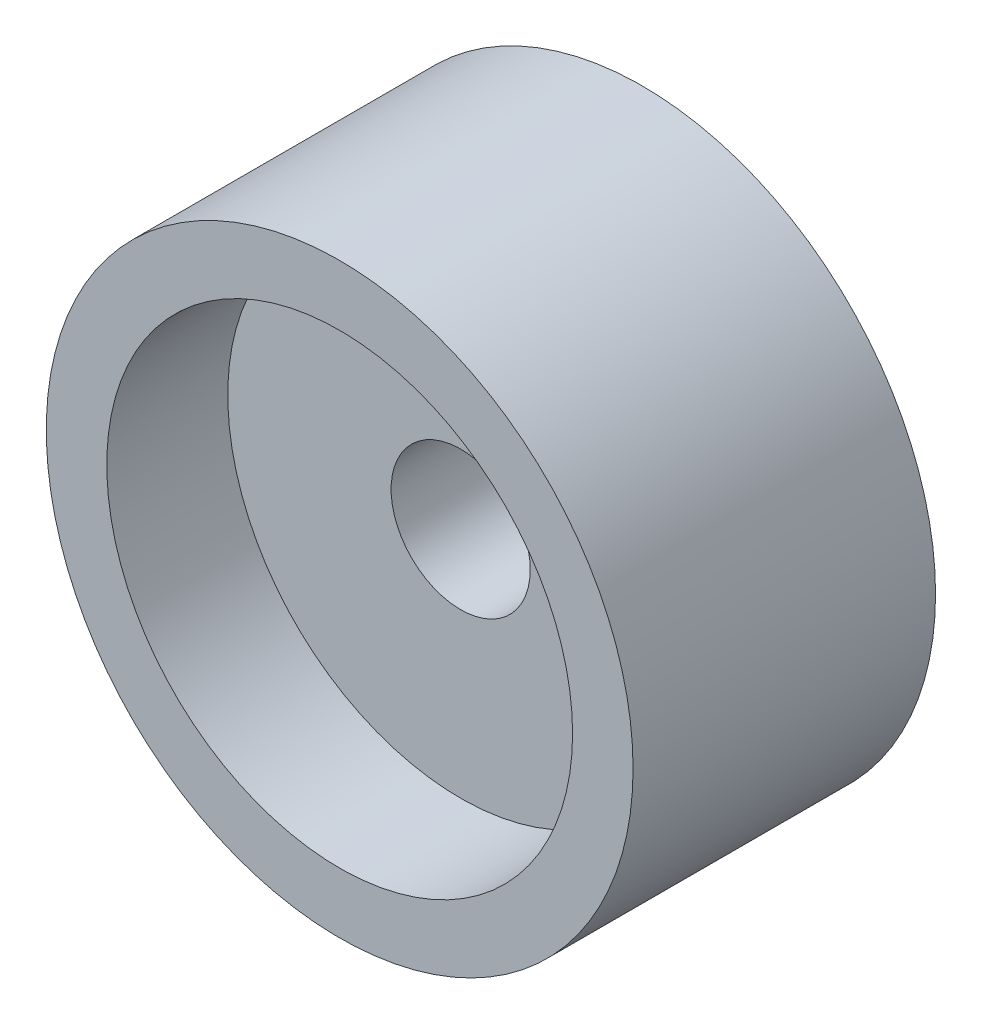
SolidWorks part; units mm, degrees
ref_plane "Front Plane" through (0, 0, 0) normal (0, 0, 1) x (1, 0, 0)
ref_plane "Top Plane" through (0, 0, 0) normal (0, 1, 0) x (1, 0, 0)
ref_plane "Right Plane" through (0, 0, 0) normal (1, 0, 0) x (0, 0, -1)
sketch "Sketch1" plane through (0, 0, 0) normal (0, 0, 1) x (1, 0, 0)
  circle A0 centre (0, 0) radius 4.85
  circle A1 centre (0, 0) radius 3.85
  circle A2 centre (0, 0) radius 1.15
  dimension "D1" = 2.3
  dimension "D2" = 7.7
  dimension "D3" = 1
extrude "Boss-Extrude1" add sketch "Sketch1" along normal blind 2 contours A0 A1 region at (-4.7128, 0, 0)
extrude "Boss-Extrude2" add sketch "Sketch1<3>" against normal blind 3 contours A1 A2 | A0 A1 region at (-4.7128, 0, 0) region at (-3.7411, 0, 0)
sketch "Sketch1<3>" plane through (0, 0, 0) normal (0, 0, 1) x (1, 0, 0) same geometry as "Sketch1"
